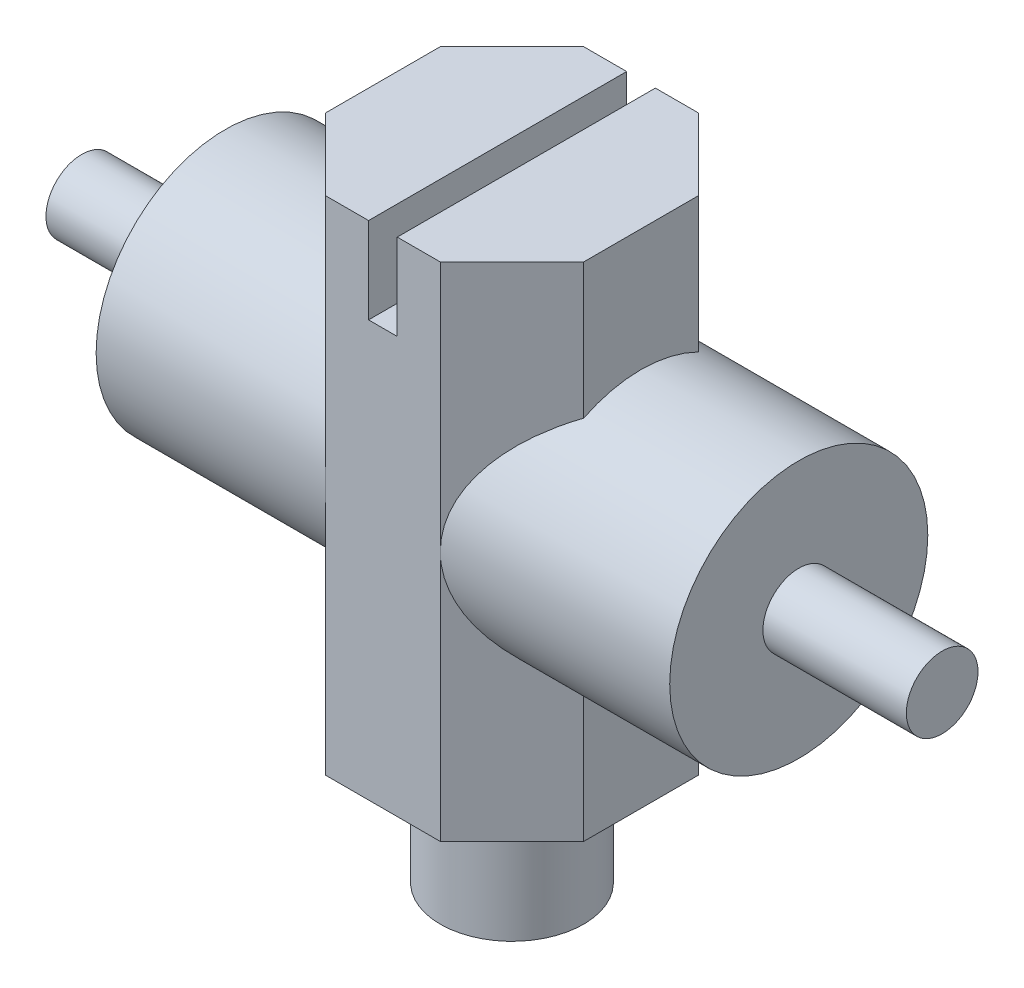
SolidWorks part; units mm, degrees
ref_plane "Front Plane" through (0, 0, 0) normal (0, 0, 1) x (1, 0, 0)
ref_plane "Top Plane" through (0, 0, 0) normal (0, 1, 0) x (1, 0, 0)
ref_plane "Right Plane" through (0, 0, 0) normal (1, 0, 0) x (0, 0, -1)
sketch "Sketch3" plane through (0, 0, 0) normal (0, 0, 1) x (1, 0, 0)
  line L0 (0, 0) -> (-126.9318, 0) construction
  line L1 (0, 0) -> (0, 25)
  line L2 (0, 25) -> (100, 25)
  line L3 (100, 25) -> (100, 90)
  line L4 (100, 90) -> (500, 90)
  line L5 (500, 90) -> (500, 25)
  line L6 (500, 25) -> (600, 25)
  line L7 (600, 25) -> (600, 0)
  line L8 (600, 0) -> (0, 0)
  dimension "D1" = 100
  dimension "D2" = 600
  dimension "D3" = 180
  dimension "D4" = 50
revolve "Revolve1" add sketch "Sketch3" angle 360 about L0
sketch "Sketch4" plane through (0, 0, 0) normal (0, 1, 0) x (1, 0, 0)
  line L0 (500, 90) -> (100, 90) construction
  line L1 (210, 90) -> (390, 90)
  line L2 (210, 90) -> (210, -90)
  line L3 (210, -90) -> (390, -90)
  line L4 (390, 90) -> (390, -90)
  line L5 (100, -90) -> (500, -90) construction
  line L6 (100, 90) -> (100, -90) construction
  line L7 (500, -90) -> (500, 90) construction
  dimension "D1" = 110
  dimension "D2" = 110
extrude "Boss-Extrude2" add sketch "Sketch4" along normal mid plane 350
sketch "Sketch5" plane through (0, -175, 0) normal (0, -1, 0) x (1, 0, 0)
  line L0 (210, 90) -> (390, -90) construction
  circle A0 centre (300, 0) radius 50
  point P6 (300, 0)
  dimension "D1" = 100
extrude "Boss-Extrude3" add sketch "Sketch5" along normal blind 90
chamfer "Chamfer1" distance 50 angle 45 8 edges at (390, 87.5, 90) (390, -87.5, 90) (210, 87.5, 90) (210, -87.5, 90) (390, 87.5, -90) (390, -87.5, -90) (210, 87.5, -90) (210, -87.5, -90)
sketch "Sketch6" plane through (0, 175, 0) normal (0, 1, 0) x (1, 0, 0)
  line L0 (340, 90) -> (260, 90) construction
  line L1 (290, 90) -> (310, 90)
  line L2 (290, 90) -> (290, -90)
  line L3 (290, -90) -> (310, -90)
  line L4 (310, 90) -> (310, -90)
  line L5 (260, -90) -> (340, -90) construction
  line L6 (390, -40) -> (390, 40) construction
  dimension "D1" = 20
  dimension "D2" = 80
extrude "Cut-Extrude1" cut sketch "Sketch6" against normal blind 60
